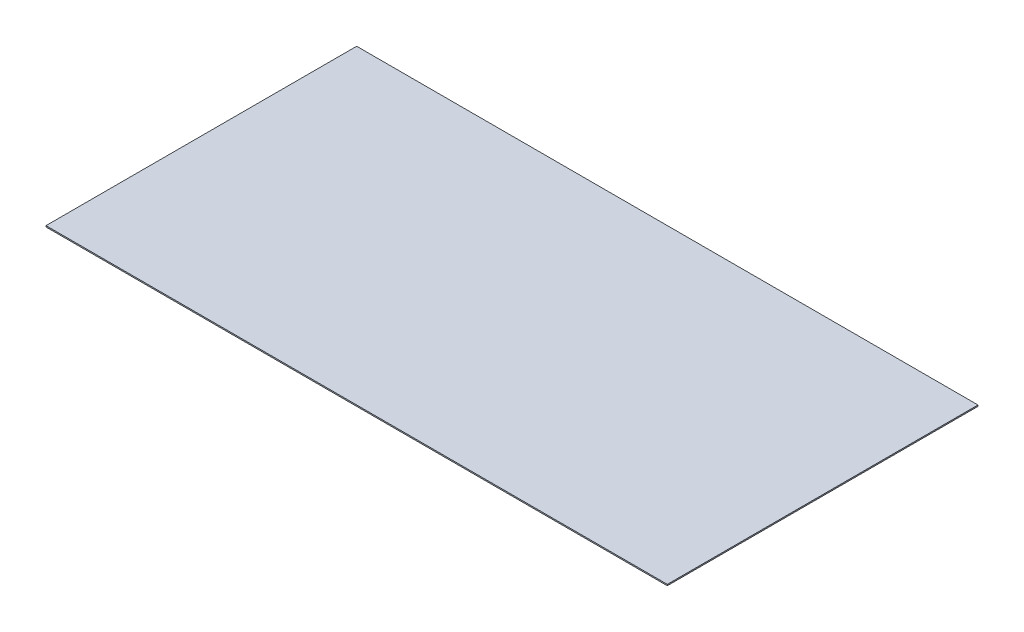
SolidWorks part; units mm, degrees
ref_plane "Front Plane" through (0, 0, 0) normal (0, 0, 1) x (1, 0, 0)
ref_plane "Top Plane" through (0, 0, 0) normal (0, 1, 0) x (1, 0, 0)
ref_plane "Right Plane" through (0, 0, 0) normal (1, 0, 0) x (0, 0, -1)
sketch "Sketch1" plane through (0, 0, 0) normal (0, 1, 0) x (1, 0, 0)
  line L1 (-1000, 500) -> (1000, 500)
  line L2 (-1000, 500) -> (-1000, -500)
  line L3 (-1000, -500) -> (1000, -500)
  line L4 (1000, 500) -> (1000, -500)
  line L5 (-1000, 500) -> (1000, -500) construction
  line L6 (-1000, -500) -> (1000, 500) construction
  point P0 (0, 0)
  dimension "D1" = 1000
  dimension "D2" = 2000
extrude "Boss-Extrude1" add sketch "Sketch1" along normal blind 4
